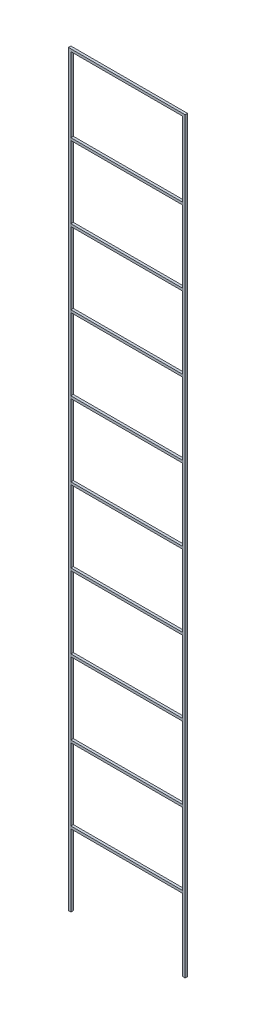
SolidWorks part; units mm, degrees
ref_plane "Front Plane" through (0, 0, 0) normal (0, 0, 1) x (1, 0, 0)
ref_plane "Top Plane" through (0, 0, 0) normal (0, 1, 0) x (1, 0, 0)
ref_plane "Right Plane" through (0, 0, 0) normal (1, 0, 0) x (0, 0, -1)
sketch "Sketch2" plane through (0, 0, 0) normal (0, 0, 1) x (1, 0, 0)
  line L0 (0, -92.3755) -> (0, -3140.3755)
  line L1 (-457.2, -92.3755) -> (-457.2, -3140.3755)
  line L2 (-457.2, -397.1755) -> (0, -397.1755)
  line L3 (-457.2, -1616.3755) -> (0, -1616.3755)
  line L4 (-457.2, -2530.7755) -> (0, -2530.7755)
  line L5 (-457.2, -701.9755) -> (0, -701.9755)
  line L6 (-457.2, -2225.9755) -> (0, -2225.9755)
  line L7 (-457.2, -1006.7755) -> (0, -1006.7755)
  line L8 (-457.2, -1311.5755) -> (0, -1311.5755)
  line L9 (-457.2, -1921.1755) -> (0, -1921.1755)
  line L10 (-457.2, -92.3755) -> (0, -92.3755)
  line L11 (-457.2, -2835.5755) -> (0, -2835.5755)
  point P26 (-228.6, -1616.3755)
  dimension "D1" = 3048
  dimension "D2" = 457.2
  dimension "D3" = 304.8
  dimension "D4" = 304.8
  dimension "D5" = 304.8
  dimension "D6" = 304.8
  dimension "D7" = 304.8
  dimension "D8" = 304.8
  dimension "D9" = 304.8
  dimension "D10" = 304.8
  dimension "D11" = 3048
extrude "Extrude-Thin1" add sketch "Sketch2" along normal blind 10 thin thin type one direction wall 10
